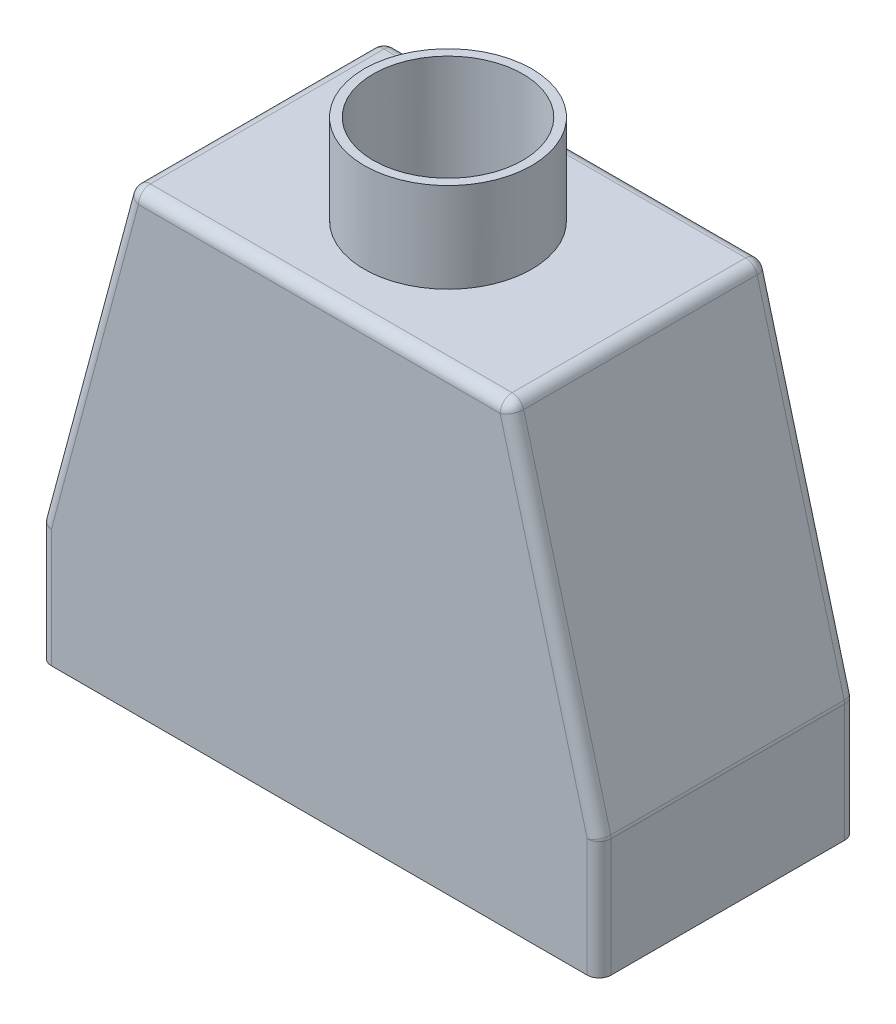
SolidWorks part; units mm, degrees
material "ABS"
ref_plane "前基準面" through (0, 0, 0) normal (0, 0, 1) x (1, 0, 0)
ref_plane "上基準面" through (0, 0, 0) normal (0, 1, 0) x (1, 0, 0)
ref_plane "右基準面" through (0, 0, 0) normal (1, 0, 0) x (0, 0, -1)
sketch "草圖1" plane through (0, 0, 0) normal (0, 0, 1) x (1, 0, 0)
  line L0 (-46.75, 0) -> (46.75, 0)
  line L1 (46.75, 0) -> (46.75, 20)
  line L2 (46.75, 20) -> (31.7448, 76)
  line L3 (31.7448, 76) -> (-31.7448, 76)
  line L4 (0, 0) -> (0, 87.7754) construction
  line L5 (-46.75, 20) -> (-31.7448, 76)
  line L6 (-46.75, 0) -> (-46.75, 20)
  dimension "D1" = 93.5
  dimension "D2" = 76
  dimension "D3" = 165
  dimension "D4" = 20
extrude "伸長1" add sketch "草圖1" along normal mid plane 43
shell "薄殼1" thickness 3 removed face at (0, 0, 0)
sketch "草圖2" plane through (0, 76, 0) normal (0, 1, 0) x (1, 0, 0)
  circle A0 centre (0, 0) radius 14
  dimension "D1" = 28
extrude "伸長2" add sketch "草圖2" along normal blind 15
sketch "草圖5" plane through (0, 91, 0) normal (0, 1, 0) x (1, 0, 0)
  circle A0 centre (0, 0) radius 12.5
  dimension "D1" = 25
extrude "除料-伸長1" cut sketch "草圖5" against normal up to next
fillet "圓角1" radius 2 4 edges at (-39.2474, 48, -21.5) (39.2474, 48, -21.5) (39.2474, 48, 21.5) (-39.2474, 48, 21.5)
fillet "圓角2" radius 2 8 edges at (31.1384, 76, 20.9142) (31.7448, 76, 0) (31.1384, 76, -20.9142) (0, 76, -21.5) (-31.1384, 76, -20.9142) (-31.7448, 76, 0) (-31.1384, 76, 20.9142) (0, 76, 21.5)
fillet "圓角3" radius 2 10 edges at (-46.75, 6.1363, 21.5) (-46.75, 17.7367, 20.9142) (-46.75, 6.1363, -21.5) (-46.75, 17.7367, -20.9142) (46.75, 6.1363, 21.5) (46.75, 17.7367, 20.9142) (46.75, 6.1363, -21.5) (46.75, 17.7367, -20.9142) (-46.75, 20, 0) (46.75, 20, 0)
